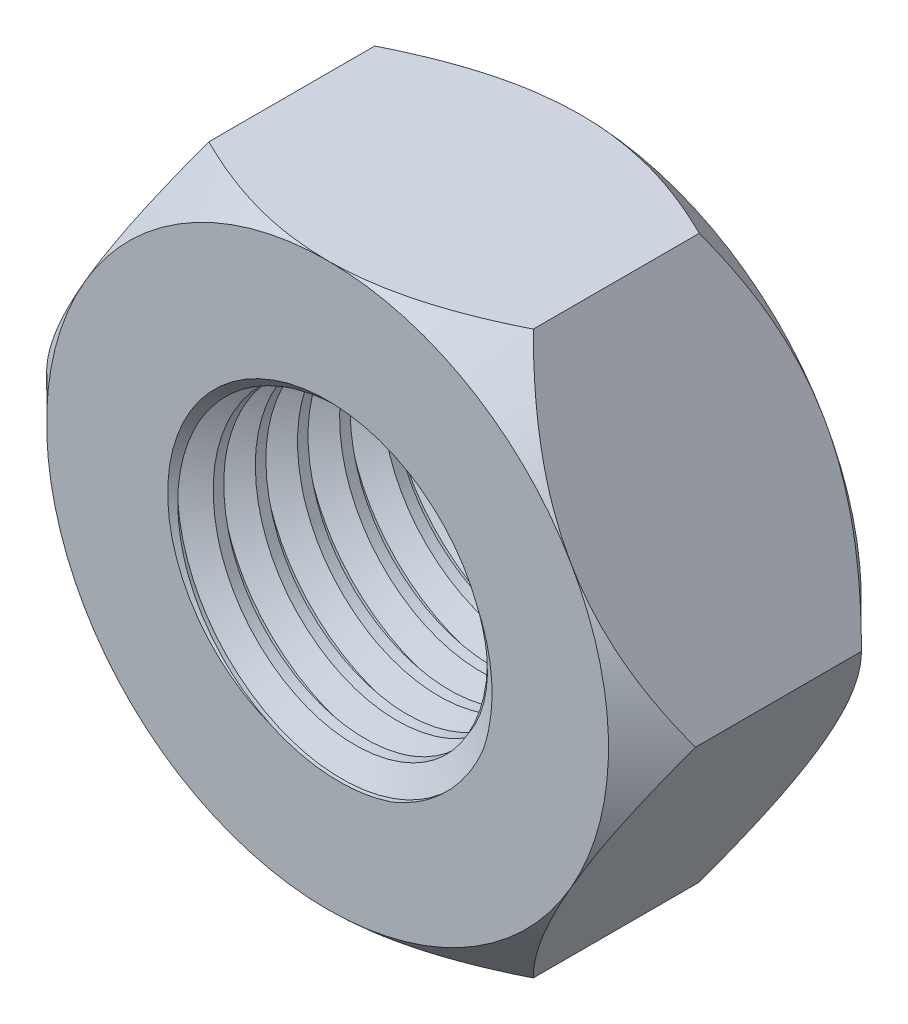
SolidWorks part; units mm, degrees
ref_plane "Front Plane" through (0, 0, 0) normal (0, 0, 1) x (1, 0, 0)
ref_plane "Top Plane" through (0, 0, 0) normal (0, 1, 0) x (1, 0, 0)
ref_plane "Right Plane" through (0, 0, 0) normal (1, 0, 0) x (0, 0, -1)
sketch "Sketch1" plane through (0, 0, 0) normal (0, 0, 1) x (1, 0, 0)
  line L1 (11.547, 0) -> (5.7735, 10)
  line L2 (5.7735, 10) -> (-5.7735, 10)
  line L3 (-5.7735, 10) -> (-11.547, 0)
  line L4 (-11.547, 0) -> (-5.7735, -10)
  line L5 (-5.7735, -10) -> (5.7735, -10)
  line L6 (5.7735, -10) -> (11.547, 0)
  circle A0 centre (0, 0) radius 10 construction
  dimension "D1" = 20
extrude "Boss-Extrude1" add sketch "Sketch1" along normal mid plane 9
sketch "Sketch2" plane through (0, 0, 4.5) normal (0, 0, 1) x (1, 0, 0)
  line L0 (5.7735, -10) -> (11.547, 0) construction
  circle A0 centre (0, 0) radius 10
extrude "Cut-Extrude1" cut sketch "Sketch2" against normal blind 9 draft 45 flip side to cut
mirror "Mirror1" about plane through (0, 0, 0) normal (0, 0, 1) of "Cut-Extrude1"
sketch "Sketch3" plane through (0, 0, 4.5) normal (0, 0, 1) x (1, 0, 0)
  circle A0 centre (0, 0) radius 5.19
  dimension "D1" = 10.38
extrude "Cut-Extrude2" cut sketch "Sketch3" against normal through all
chamfer "Chamfer1" distance 0.5 angle 45 2 edges at (5.19, 0, -4.5) (5.19, 0, 4.5)
thread "Thread1" pitch 1.5 method cut profile "Thread Profile1" start angle 0, offset 2, length 0, pitch 1.5, diameter 10.38
ref_plane "Plane1" through (-5.19, 0, 6) normal (0, -1, 0) x (-1, 0, 0)
sketch "Thread Profile1" plane through (-5.19, 0, 6) normal (0, -1, 0) x (-1, 0, 0)
  line L0 (0, 0) -> (0, 1.5) construction
  line L1 (0, 0) -> (0.8119, 0.4687)
  line L2 (0.8119, 0.4687) -> (0.8119, 0.6562)
  line L3 (0.8119, 0.6562) -> (0, 1.125)
  line L4 (0.8119, 0.5625) -> (0, 0.5625) construction
  line L11 (0, 0) -> (0, 1.125)
  point P2 (0, 0)
  dimension "Pitch" = 1.5
  dimension "Profile_Angle" = 60
  dimension "Profile_Land" = 0.1875
  dimension "Profile_Height" = 0.8119
